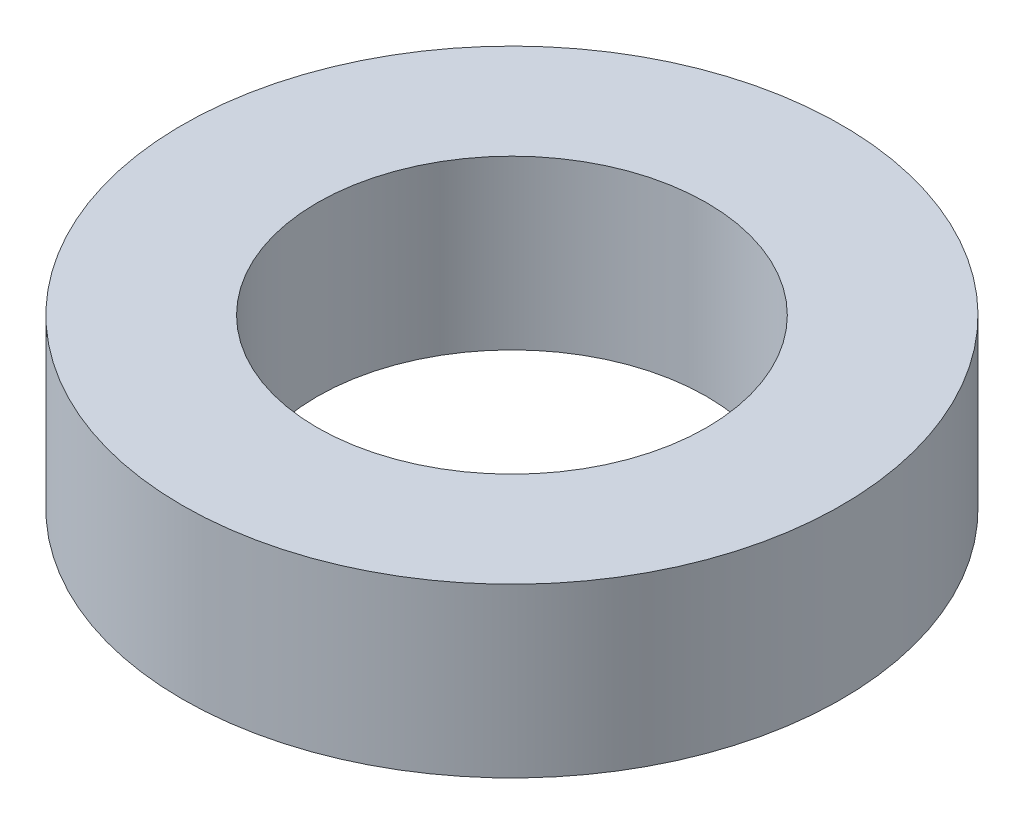
SolidWorks part; units mm, degrees
ref_plane "Front Plane" through (0, 0, 0) normal (0, 0, 1) x (1, 0, 0)
ref_plane "Top Plane" through (0, 0, 0) normal (0, 1, 0) x (1, 0, 0)
ref_plane "Right Plane" through (0, 0, 0) normal (1, 0, 0) x (0, 0, -1)
sketch "Sketch1" plane through (0, 0, 0) normal (0, 1, 0) x (1, 0, 0)
  circle A0 centre (0, 0) radius 55
  dimension "FLANGE_OD" = 110
extrude "Boss-Extrude1" add sketch "Sketch1" along normal blind 28
sketch "Sketch2" plane through (0, 0, 0) normal (0, 1, 0) x (1, 0, 0)
  circle A0 centre (0, 0) radius 32.5
  dimension "BORE_D" = 65
extrude "Cut-Extrude1" cut sketch "Sketch2" along normal through all
sketch "Sketch3" plane through (0, 28, 0) normal (0, 1, 0) x (1, 0, 0)
  circle A0 centre (0, 0) radius 24.9085 construction
  circle A1 centre (-24.9085, 0) radius 3.0916
  dimension "BOLT_D" = 6.1831
  dimension "BOLT_PCD" = 49.8169
extrude "Cut-Extrude2" cut sketch "Sketch3" against normal blind 18.8417 rebuild error yes
pattern_circular "CirPattern1" count 6 over 360 rebuild error yes
